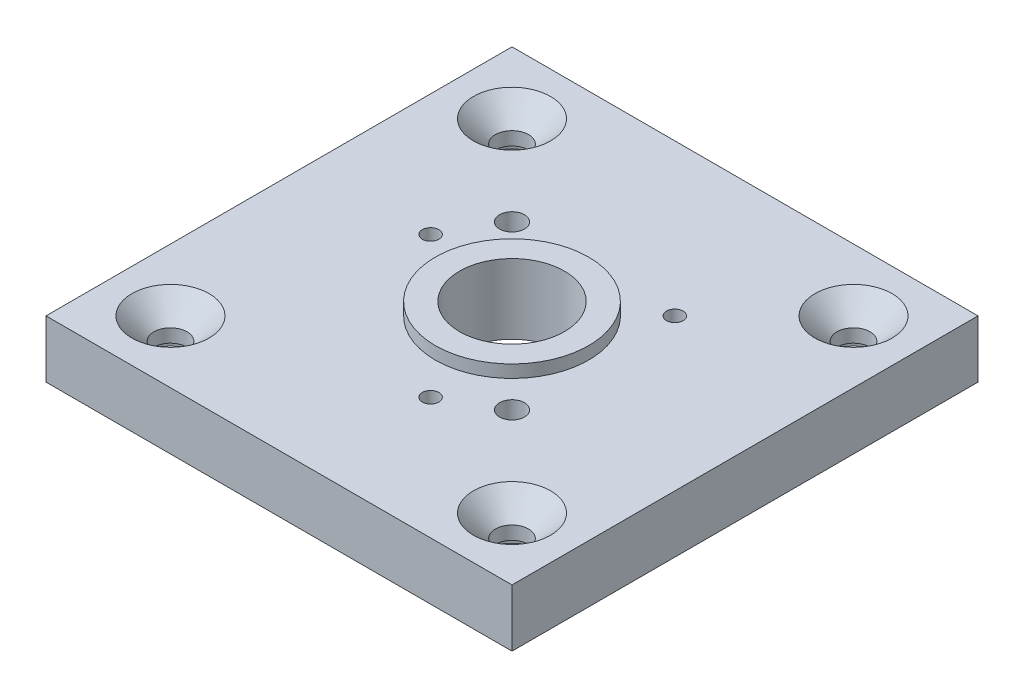
SolidWorks part; units mm, degrees
ref_plane "Front Plane" through (0, 0, 0) normal (0, 0, 1) x (1, 0, 0)
ref_plane "Top Plane" through (0, 0, 0) normal (0, 1, 0) x (1, 0, 0)
ref_plane "Right Plane" through (0, 0, 0) normal (1, 0, 0) x (0, 0, -1)
sketch "Sketch1" plane through (0, 0, 0) normal (0, 1, 0) x (1, 0, 0)
  line L0 (0, 42.3) -> (42.3, 0) construction
  line L1 (0, 0) -> (42.3, 0)
  line L2 (0, 0) -> (0, 42.3)
  line L3 (0, 42.3) -> (42.3, 42.3)
  line L4 (42.3, 0) -> (42.3, 42.3)
  line L6 (36.65, 36.65) -> (5.65, 36.65) construction
  line L7 (36.65, 36.65) -> (36.65, 5.65) construction
  line L8 (36.65, 5.65) -> (5.65, 5.65) construction
  line L9 (5.65, 36.65) -> (5.65, 5.65) construction
  line L10 (36.65, 36.65) -> (5.65, 5.65) construction
  line L11 (36.65, 5.65) -> (5.65, 36.65) construction
  circle A0 centre (36.65, 36.65) radius 1.5
  circle A1 centre (5.65, 5.65) radius 1.5
  circle A2 centre (36.65, 5.65) radius 1.5
  circle A3 centre (5.65, 36.65) radius 1.5
  circle A4 centre (21.15, 21.15) radius 4.7625
  point P5 (21.15, 21.15)
  dimension "D4" = 3
  dimension "D5" = 3
  dimension "D6" = 3
  dimension "D7" = 3
  dimension "D8" = 9.525
  dimension "D1" = 42.3
  dimension "D2" = 42.3
  dimension "D3" = 31
extrude "Boss-Extrude1" add sketch "Sketch1" along normal blind 5.21
sketch "Sketch2" plane through (0, 5.21, 0) normal (0, 1, 0) x (1, 0, 0)
  line L0 (21.15, 21.15) -> (42.3, 21.15) construction
  line L1 (42.3, 0) -> (42.3, 42.3) construction
  line L2 (21.15, 21.15) -> (28.5393, 28.5393) construction
  line L3 (5.65, 36.65) -> (36.65, 5.65) construction
  circle A0 centre (21.15, 21.15) radius 10.45 construction
  circle A1 centre (11.0561, 23.8547) radius 0.7557
  circle A2 centre (28.5393, 28.5393) radius 0.7556
  circle A3 centre (23.8547, 11.0561) radius 0.7556
  circle A4 centre (28.5393, 13.7607) radius 1.1303
  circle A5 centre (13.7607, 28.5393) radius 1.1303
  point P11 (21.15, 21.15)
  point P23 (21.15, 21.15)
  dimension "D1" = 1.5113
  dimension "D3" = 20.9
  dimension "D5" = 2.2606
  dimension "D4" = 45
  dimension "D2" = 3
  dimension "D6" = 2
extrude "Cut-Extrude1" cut sketch "Sketch2" against normal through all
chamfer "Chamfer1" distance 2 angle 45 4 edges at (5.65, 5.21, -4.15) (36.65, 5.21, -4.15) (36.65, 5.21, -35.15) (5.65, 5.21, -35.15)
sketch "Sketch3" [suppressed] plane through (0, 3.175, 0) normal (0, 1, 0) x (1, 0, 0)
  line L1 (21.175, 36.68) -> (21.125, 36.68)
  line L2 (36.675, 21.18) -> (36.675, -10.46)
  line L3 (36.675, -10.46) -> (5.625, -10.46)
  line L4 (5.625, 21.18) -> (5.625, -10.46)
  circle A0 centre (21.15, 21.15) radius 4.7625 construction
  circle A1 centre (21.15, 21.15) radius 4.7625 construction
  arc A2 (21.175, 36.68) -> (36.675, 21.18) centre (21.175, 21.18) cw
  arc A3 (21.125, 36.68) -> (5.625, 21.18) centre (21.125, 21.18) ccw
  point P9 (36.675, 36.68)
  dimension "D5" = 15.5
  dimension "D1" = 31.05
  dimension "D2" = 47.14
  dimension "D3" = 31.61
  dimension "D4" = 15.525
sketch "Sketch4" plane through (0, 5.21, 0) normal (0, 1, 0) x (1, 0, 0)
  circle A0 centre (21.15, 21.15) radius 4.7625 construction
  circle A1 centre (21.15, 21.15) radius 4.7625
  circle A2 centre (21.15, 21.15) radius 6.96
  dimension "D1" = 13.92
extrude "Boss-Extrude2" add sketch "Sketch4" along normal blind 1.14
sketch "Sketch5" plane through (0, 0, 0) normal (0, -1, 0) x (1, 0, 0)
  circle A0 centre (5.65, -5.65) radius 1.5 construction
  circle A1 centre (36.65, -5.65) radius 1.5 construction
  circle A2 centre (5.65, -36.65) radius 1.5 construction
  circle A3 centre (36.65, -36.65) radius 1.5 construction
  circle A4 centre (5.65, -5.65) radius 1.5
  circle A5 centre (36.65, -5.65) radius 1.5
  circle A6 centre (5.65, -36.65) radius 1.5
  circle A7 centre (36.65, -36.65) radius 1.5
  circle A8 centre (36.65, -36.65) radius 4
  circle A9 centre (21.15, -21.15) radius 4.7625 construction
  circle A10 centre (21.15, -21.15) radius 4.7625 construction
  circle A11 centre (5.65, -36.65) radius 4
  circle A12 centre (5.65, -5.65) radius 4
  circle A13 centre (36.65, -5.65) radius 4
  point P25 (21.15, -21.15)
  dimension "D1" = 8
  dimension "D2" = 4
extrude "Cut-Extrude2" cut sketch "Sketch5" against normal blind 2
equation "\"D5@Sketch1\"=\"D4@Sketch1\""
equation "\"D6@Sketch1\"=\"D4@Sketch1\""
equation "\"D7@Sketch1\"=\"D4@Sketch1\""
equation "\"D8@Sketch1\"=.375in"
equation "\"D4@Sketch3\"=\"D1@Sketch3\"/2"
